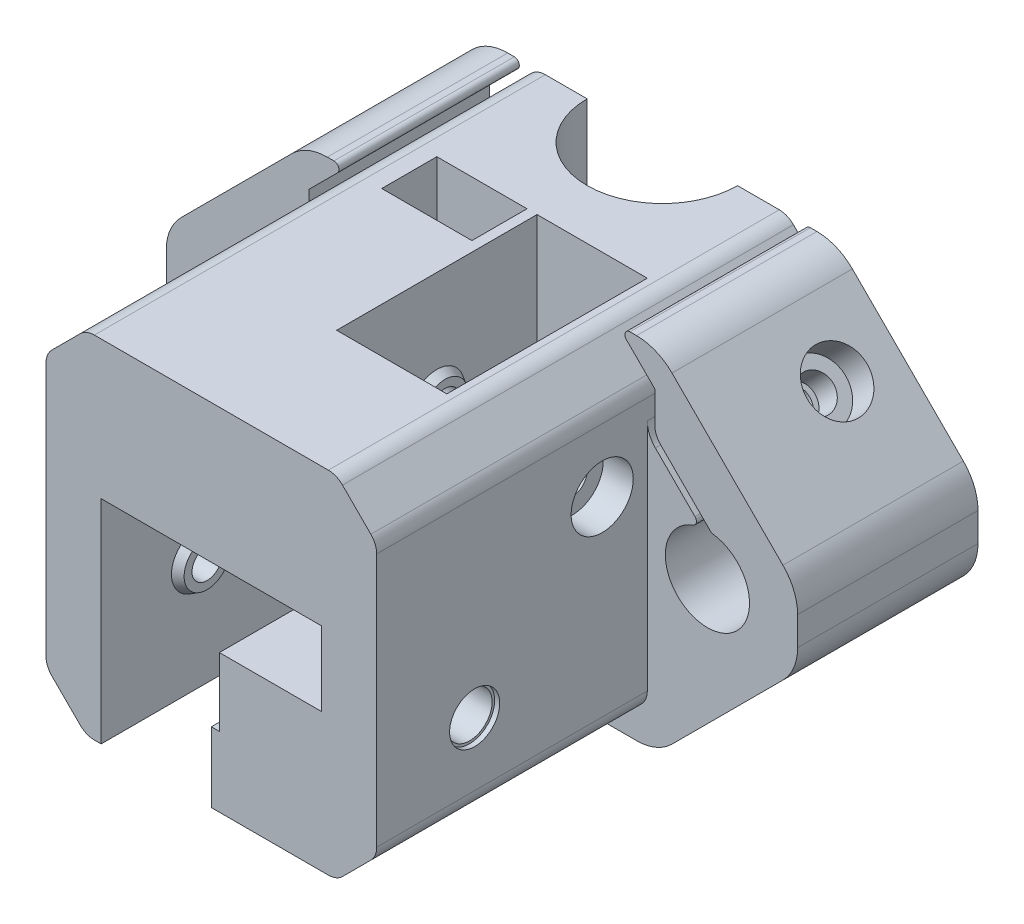
SolidWorks part; units mm, degrees
ref_plane "XY" through (0, 0, 0) normal (0, 0, 1) x (1, 0, 0)
ref_plane "XZ" through (0, 0, 0) normal (0, 1, 0) x (1, 0, 0)
ref_plane "YZ" through (0, 0, 0) normal (1, 0, 0) x (0, 0, -1)
sketch "Sketch1" plane through (0, 0, 0) normal (0, 0, 1) x (1, 0, 0)
  line L0 (-17.5, 17.5) -> (-31.5, 3.5)
  line L1 (31.5, -17.5) -> (17.5, -17.5) construction
  line L2 (31.5, -17.5) -> (31.5, -3.5) construction
  line L3 (31.5, 17.5) -> (17.5, 17.5) construction
  line L4 (-31.5, -17.5) -> (-31.5, -3.5) construction
  line L5 (31.5, -17.5) -> (-31.5, 17.5) construction
  line L6 (31.5, 17.5) -> (-31.5, -17.5) construction
  line L7 (-12.5, 17.5) -> (-16.5, 13.5)
  line L8 (-16.5, 13.5) -> (-16.5, 9.535)
  line L9 (-16.5, 9.535) -> (-21.8809, 4.1541)
  line L10 (-13.5607, 17.5) -> (-17.25, 13.8107)
  line L11 (-17.25, 13.8107) -> (-17.25, 9.8457)
  line L12 (-17.25, 9.8457) -> (-22.9163, 4.1793)
  line L13 (-17.25, 9.8457) -> (-22.4112, 4.6844) construction
  line L14 (-13.0303, 18.0303) -> (-17.25, 13.8107) construction
  line L15 (-13.5607, 17.5) -> (-17.5, 17.5)
  line L16 (0, 0) -> (-59.6161, 0) construction
  line L17 (0, 0) -> (0, 36.6742) construction
  line L18 (-17.5, -17.5) -> (-31.5, -3.5)
  line L19 (17.5, -17.5) -> (31.5, -3.5)
  line L20 (16.5, 9.535) -> (21.8809, 4.1541)
  line L21 (16.5, 13.5) -> (16.5, 9.535)
  line L22 (12.5, 17.5) -> (16.5, 13.5)
  line L23 (13.5607, 17.5) -> (17.25, 13.8107)
  line L24 (17.25, 13.8107) -> (17.25, 9.8457)
  line L25 (17.25, 9.8457) -> (22.9163, 4.1793)
  line L26 (17.5, 17.5) -> (31.5, 3.5)
  line L27 (12.5, 17.5) -> (-12.5, 17.5)
  line L28 (-17.5, 17.5) -> (-31.5, 17.5) construction
  line L29 (-31.5, 3.5) -> (-31.5, 17.5) construction
  line L30 (-31.5, -3.5) -> (-31.5, 3.5)
  line L31 (-17.5, -17.5) -> (-31.5, -17.5) construction
  line L32 (17.5, -17.5) -> (-17.5, -17.5)
  line L33 (31.5, -3.5) -> (31.5, 3.5)
  line L34 (31.5, 3.5) -> (31.5, 17.5) construction
  line L35 (17.5, 17.5) -> (13.5607, 17.5)
  arc A0 (-22.9163, 4.1793) -> (-21.8809, 4.1541) centre (-22.5, 0) ccw
  arc A1 (22.9163, 4.1793) -> (21.8809, 4.1541) centre (22.5, 0) cw
  point P0 (0, 0)
  dimension "D1" = 63
  dimension "D6" = 8.4
  dimension "D2" = 35
  dimension "D3" = 14
  dimension "D4" = 14
  dimension "D5" = 22.5
  dimension "D7" = 19
  dimension "D8" = 15
  dimension "D9" = 9.535
  dimension "D10" = 0.75
extrude "Boss-Extrude1" add sketch "Sketch1" along normal blind 18
sketch "Sketch2" plane through (0, 17.5, 0) normal (0, 1, 0) x (1, 0, 0)
  line L0 (12.5, 0) -> (-12.5, 0) construction
  line L1 (12.5, -18) -> (-12.5, -18) construction
  line L2 (-10, -18) -> (-1, -18)
  line L3 (-10, -18) -> (-10, -12.5)
  line L4 (-10, -12.5) -> (-1, -12.5)
  line L5 (-1, -18) -> (-1, -12.5)
  circle A0 centre (0, 0) radius 7.5
  point P10 (-5.5, -12.5)
  dimension "D1" = 15
  dimension "D2" = 9
  dimension "D3" = 5.5
  dimension "D4" = 5.5
extrude "Cut-Extrude1" cut sketch "Sketch2" against normal through all
fillet "Fillet1" radius 5 8 edges at (17.5, 17.5, 9) (31.5, 3.5, 9) (31.5, -3.5, 9) (17.5, -17.5, 9) (-17.5, -17.5, 9) (-31.5, -3.5, 9) (-31.5, 3.5, 9) (-17.5, 17.5, 9)
fillet "Fillet2" radius 0.5 6 edges at (-22.9163, 4.1793, 9) (-21.8809, 4.1541, 9) (21.8809, 4.1541, 9) (22.9163, 4.1793, 9) (-13.5607, 17.5, 9) (13.5607, 17.5, 9)
fillet "Fillet3" radius 2 2 edges at (17.25, 9.8457, 9) (-17.25, 9.8457, 9)
fillet "Fillet4" radius 2.75 2 edges at (-16.5, 9.535, 9) (16.5, 9.535, 9)
sketch "Sketch3" plane through (-17.5, 17.5, 0) normal (-0.7071, 0.7071, 0) x (0, 0, 1)
  line L0 (0, -2.0711) -> (0, -17.7279) construction
  circle A0 centre (6, -8.4) radius 1.75
  point P6 (-12.8431, 2.7076)
  dimension "D1" = 3.5
  dimension "D2" = 6
  dimension "D3" = 8.4
ref_plane "Plane1" through (0, 0, 6) normal (0, 0, -1) x (-1, 0, 0)
sketch "Sketch4" plane through (0, 0, 6) normal (0, 0, -1) x (-1, 0, 0)
  line L0 (23.4397, 11.5603) -> (11.3618, -0.5176) construction
  line L1 (24.6771, 10.3229) -> (22.2023, 12.7977) construction
  line L2 (23.4397, 11.5603) -> (25.561, 9.439)
  line L3 (18.9645, 16.0355) -> (30.0355, 4.9645) construction
  line L4 (25.561, 9.439) -> (23.4397, 7.3177)
  line L5 (23.4397, 7.3177) -> (22.5558, 8.2015)
  line L6 (12.8331, 0.9537) -> (23.4397, 11.5603)
  line L9 (22.5558, 8.2015) -> (14.0705, -0.2837)
  line L10 (14.0705, -0.2837) -> (12.8331, 0.9537)
  dimension "D1" = 3
  dimension "D2" = 1.75
  dimension "D3" = 3
  dimension "D4" = 15
revolve "Cut-Revolve1" cut sketch "Sketch4" angle 360 about L0
sketch "Sketch6" plane through (-6.8934, 6.8934, 0) normal (-0.7071, 0.7071, 0) x (0, 0, 1)
  line L0 (0, -2.0711) -> (0, -17.7279) construction
  line L1 (3.425, -9.8867) -> (6, -11.3734)
  line L2 (6, -11.3734) -> (8.575, -9.8867)
  line L3 (8.575, -9.8867) -> (8.575, -6.9133)
  line L4 (8.575, -6.9133) -> (6, -5.4266)
  line L5 (6, -5.4266) -> (3.425, -6.9133)
  line L6 (3.425, -6.9133) -> (3.425, -9.8867)
  circle A0 centre (6, -8.4) radius 2.575 construction
  dimension "D1" = 5.15
extrude "Cut-Extrude2" cut sketch "Sketch6" against normal blind 15
mirror "Mirror1" about plane through (0, 0, 0) normal (1, 0, 0) of "Cut-Extrude2", "Cut-Revolve1"
sketch "Sketch7" plane through (0, 0, 0) normal (0, 0, -1) x (-1, 0, 0)
  circle A0 centre (-12.5, 12.5) radius 1.6
  dimension "D1" = 3.2
  dimension "D2" = 12.5
  dimension "D3" = 12.5
extrude "Cut-Extrude3" cut sketch "Sketch7" against normal blind 10
sketch "Sketch8" plane through (0, 0, 0) normal (0, 0, -1) x (-1, 0, 0)
  circle A0 centre (-12.5, 12.5) radius 2.35
  dimension "D1" = 4.7
extrude "Cut-Extrude4" cut sketch "Sketch8" against normal blind 5
sketch "Sketch9" plane through (0, 0, 0) normal (0, 0, -1) x (-1, 0, 0)
  circle A0 centre (-12.5, 12.5) radius 2.5
  dimension "D1" = 5
extrude "Cut-Extrude5" cut sketch "Sketch9" against normal blind 0.5
mirror "Mirror2" about plane through (0, 0, 0) normal (0, 1, 0) of "Cut-Extrude5", "Cut-Extrude4", "Cut-Extrude3"
mirror "Mirror3" about plane through (0, 0, 0) normal (1, 0, 0) of "Mirror2", "Cut-Extrude5", "Cut-Extrude4", "Cut-Extrude3"
sketch "Sketch10" plane through (0, 0, 18) normal (0, 0, 1) x (1, 0, 0)
  line L0 (12.5, 17.5) -> (-1, 17.5) construction
  line L1 (16.5, 13.5) -> (12.5, 17.5) construction
  line L2 (16.5, 10.6741) -> (16.5, 13.5) construction
  line L3 (12.5, 17.5) -> (-12.5, 17.5)
  line L4 (16.5, 13.5) -> (12.5, 17.5)
  line L5 (16.5, -13.5) -> (16.5, 13.5)
  line L6 (0, -17.5) -> (0, 17.5) construction
  line L7 (0, 0) -> (16.5, 0) construction
  line L8 (-16.5, -13.5) -> (-16.5, 13.5)
  line L9 (-16.5, 13.5) -> (-12.5, 17.5)
  line L10 (-16.5, -13.5) -> (-12.5, -17.5)
  line L11 (16.5, -13.5) -> (12.5, -17.5)
  line L12 (12.5, -17.5) -> (-12.5, -17.5)
  point P14 (-16.5, 0)
extrude "Boss-Extrude2" add sketch "Sketch10" along normal offset from surface (27 mm away) 45 up to face at (-10, -12.5, 0)
sketch "Sketch11" plane through (0, 17.5, 0) normal (0, 1, 0) x (1, 0, 0)
  line L0 (-1, -12.5) -> (-10, -12.5) construction
  line L1 (0, -12.5) -> (11, -12.5)
  line L2 (0, -12.5) -> (0, -32.5)
  line L3 (0, -32.5) -> (11, -32.5)
  line L4 (11, -12.5) -> (11, -32.5)
  dimension "D1" = 20
  dimension "D2" = 11
extrude "Cut-Extrude6" cut sketch "Sketch11" against normal blind 21.2
sketch "Sketch12" plane through (0, 0, 32.5) normal (0, 0, -1) x (-1, 0, 0)
  line L0 (0, -3.7) -> (-11, -3.7) construction
  line L1 (0, -3.7) -> (-11, -3.7)
  line L2 (0, 0) -> (-16.491, 0) construction
  line L3 (-11, -3.7) -> (-11, 3.7)
  line L4 (-11, 3.7) -> (0, 3.7)
  line L5 (0, 3.7) -> (0, -3.7)
  line L6 (0, -3.7) -> (0, -3.5912)
  line M2 (-11, 17.5) -> (-11, -3.7)
  line M3 (-11, -3.7) -> (0, -3.7)
  line M4 (0, -3.7) -> (0, 17.5)
extrude "Cut-Extrude7" cut sketch "Sketch12" against normal up to surface (12.5 mm away) contours L2 L4 M4 M2 | L5 L2 L3 M3 M4 region at (5.5, -1.85, 32.5) region at (5.5, 1.85, 32.5) up to face at (0, 0, 45)
fillet "Fillet5" radius 10 1 edges at (5.5, -3.7, 12.5)
sketch "Sketch13" plane through (0, -17.5, 0) normal (0, -1, 0) x (1, 0, 0)
  line L1 (0, 45) -> (-11, 45)
  line L2 (0, 45) -> (0, 25.2)
  line L3 (0, 25.2) -> (-11, 25.2)
  line L4 (-11, 45) -> (-11, 25.2)
  dimension "D1" = 11
  dimension "D2" = 19.8
extrude "Cut-Extrude8" cut sketch "Sketch13" against normal up to surface (21.2 mm away) up to face at (5.5, 3.7, 38.75)
fillet "Fillet6" radius 10 1 edges at (-5.5, 3.7, 25.2) tangent propagation no
sketch "Sketch14" plane through (0, 0, 45) normal (0, 0, 1) x (1, 0, 0)
  line L0 (-11, 3.7) -> (11, 3.7) construction
  line L1 (11, -3.7) -> (11, 3.7) construction
  line L2 (0, -3.7) -> (11, -3.7) construction
  line L3 (0, 3.7) -> (11, 3.7)
  line L4 (11, -3.7) -> (11, 3.7)
  line L5 (0, -3.7) -> (11, -3.7)
  line L6 (0, -3.7) -> (0, 3.7)
extrude "Cut-Extrude9" cut sketch "Sketch14" against normal up to surface (12.5 mm away) up to face at (5.5, 10.4143, 32.5)
sketch "Sketch15" plane through (-11, 0, 0) normal (1, 0, 0) x (0, 0, -1)
  circle A0 centre (-35.23, -6.365) radius 2.75
  dimension "D1" = 5.5
  dimension "D2" = 35.23
  dimension "D3" = 6.365
extrude "Boss-Extrude3" add sketch "Sketch15" along normal blind 0.8 draft 30
sketch "Sketch16" plane through (0, 0, 0) normal (-1, 0, 0) x (0, 0, 1)
  line L1 (45, -3.7) -> (31, -3.7)
  line L2 (45, -3.7) -> (45, -10.515)
  line L3 (45, -10.515) -> (31, -10.515)
  line L4 (31, -3.7) -> (31, -10.515)
  dimension "D1" = 6.815
  dimension "D2" = 14
extrude "Cut-Extrude10" cut sketch "Sketch16" against normal blind 0.8
ref_plane "Plane2" through (0, 0, 35.23) normal (0, 0, 1) x (1, 0, 0)
sketch "Sketch17" plane through (0, 0, 35.23) normal (0, 0, 1) x (1, 0, 0)
  line L0 (31.9477, -6.365) -> (-32.235, -6.365) construction
  line L2 (-11, -9.115) -> (-11, -3.615) construction
  line L3 (-11, -9.115) -> (-11, -3.615) construction
  line L4 (-16.5, -6.365) -> (-16.5, -3.265)
  line L5 (-16.5, 10.6741) -> (-16.5, -13.5) construction
  line L6 (-16.5, -3.265) -> (-13.5, -3.265)
  line L7 (-13.5, -3.265) -> (-13.5, -4.865)
  line L8 (-13.5, -4.865) -> (11.5, -4.865)
  line L9 (11.5, -4.865) -> (11.5, -4.115)
  line L10 (11.5, -4.115) -> (16, -4.115)
  line L11 (16, -4.115) -> (16, -3.865)
  line L12 (16, -3.865) -> (16.5, -3.865)
  line L13 (16.5, 13.5) -> (16.5, -13.5) construction
  line L14 (16.5, -3.865) -> (16.5, -6.365)
  line L15 (16.5, -13.5) -> (16.5, 10.6741) construction
  line L16 (16.5, -6.365) -> (-16.5, -6.365)
  point P5 (-11, -6.365)
  dimension "D1" = 3
  dimension "D2" = 3.1
  dimension "D3" = 1.5
  dimension "D4" = 2.25
  dimension "D5" = 2.5
  dimension "D6" = 0.5
  dimension "D7" = 5
revolve "Cut-Revolve2" cut sketch "Sketch17" angle 360 about L0
sketch "Sketch18" plane through (11, 0, 0) normal (-1, 0, 0) x (0, 0, 1)
  circle A0 centre (22.5, 6.365) radius 1.5
  dimension "D1" = 6.365
  dimension "D3" = 3
  dimension "D2" = 22.5
sketch "Sketch19" plane through (11, 0, 0) normal (-1, 0, 0) x (0, 0, 1)
  circle A0 centre (22.5, 6.365) radius 2.75
  dimension "D1" = 5.5
extrude "Boss-Extrude4" add sketch "Sketch19" along normal blind 0.8 draft 30
ref_plane "Plane3" through (5.5, 0, 0) normal (1, 0, 0) x (0, 0, -1)
mirror "Mirror4" about plane through (5.5, 0, 0) normal (1, 0, 0) of "Boss-Extrude4"
ref_plane "Plane4" through (0, 0, 22.5) normal (0, 0, 1) x (1, 0, 0)
sketch "Sketch20" plane through (0, 0, 22.5) normal (0, 0, 1) x (1, 0, 0)
  line L0 (11, 6.365) -> (-21.7769, 6.365) construction
  line L1 (16.5, 6.365) -> (16.5, 9.465)
  line L2 (16.5, 13.5) -> (16.5, -13.5) construction
  line L3 (16.5, 9.465) -> (13.5, 9.465)
  line L4 (13.5, 9.465) -> (13.5, 7.865)
  line L5 (13.5, 7.865) -> (-11.5, 7.865)
  line L6 (-11.5, 7.865) -> (-11.5, 8.615)
  line L7 (-11.5, 8.615) -> (-16, 8.615)
  line L8 (-16, 8.615) -> (-16, 8.865)
  line L9 (-16, 8.865) -> (-16.5, 8.865)
  line L10 (-16.5, -13.5) -> (-16.5, 13.5) construction
  line L11 (-16.5, 8.865) -> (-16.5, 6.365)
  line L12 (-16.5, 10.6741) -> (-16.5, -13.5) construction
  line L13 (-16.5, 6.365) -> (16.5, 6.365)
  dimension "D1" = 3.1
  dimension "D2" = 3
  dimension "D3" = 1.5
  dimension "D4" = 2.25
  dimension "D5" = 2.5
  dimension "D6" = 0.5
  dimension "D7" = 25
revolve "Cut-Revolve3" cut sketch "Sketch20" angle 360 about L0
fillet "Fillet7" radius 2 8 edges at (16.5, -13.5, 31.5) (12.5, -17.5, 31.5) (-12.5, -17.5, 31.5) (-16.5, -13.5, 31.5) (16.5, 13.5, 22.5) (12.5, 17.5, 22.5) (-12.5, 17.5, 22.5) (-16.5, 13.5, 22.5)
